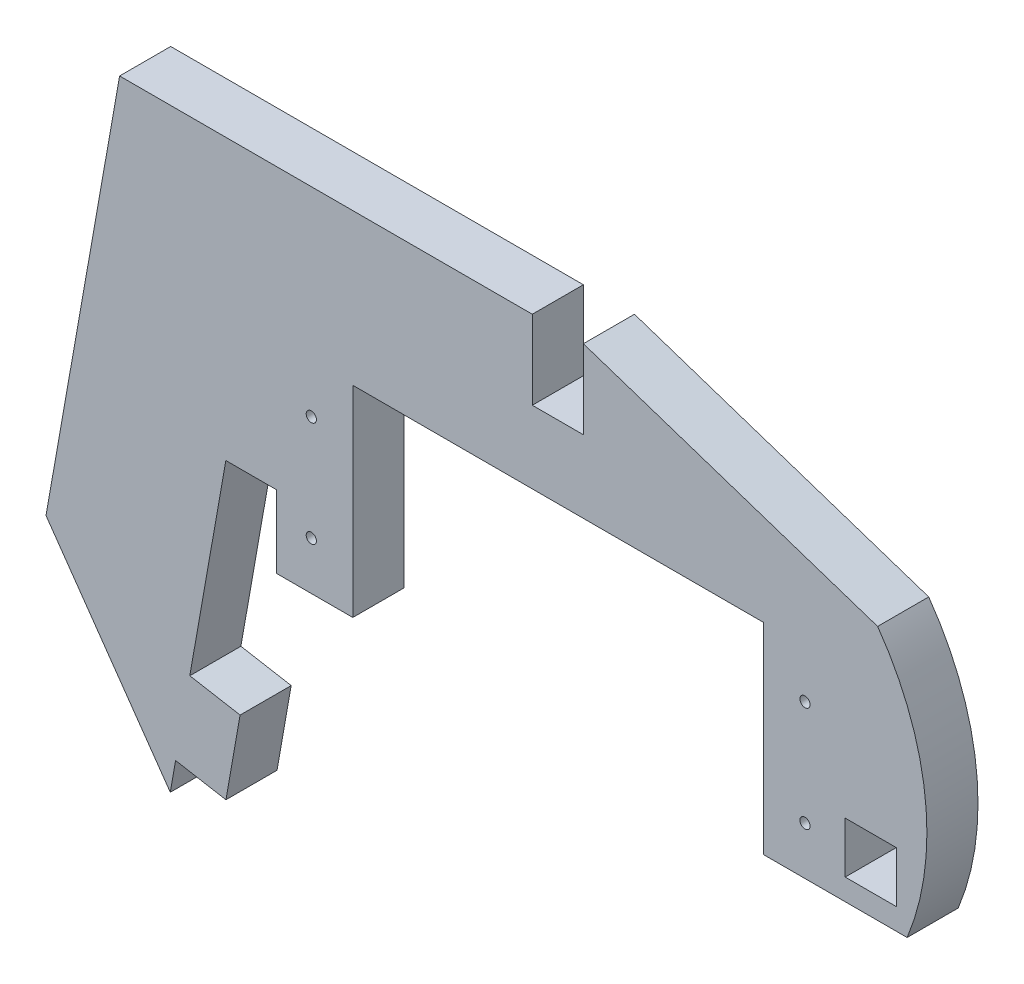
SolidWorks part; units mm, degrees
material "Balsa"
ref_plane "Plan de face" through (0, 0, 0) normal (0, 0, 1) x (1, 0, 0)
ref_plane "Plan de dessus" through (0, 0, 0) normal (0, 1, 0) x (1, 0, 0)
ref_plane "Plan de droite" through (0, 0, 0) normal (1, 0, 0) x (0, 0, -1)
sketch "Esquisse1" plane through (0, 0, 0) normal (0, 0, 1) x (1, 0, 0)
  line L0 (0, 0) -> (0, -19.685)
  line L1 (0, -19.685) -> (20, -19.685)
  line L2 (20, -19.685) -> (20, 2.315)
  line L3 (20, 2.315) -> (-17.6294, 14.8091)
  line L4 (-63.0278, 14.8091) -> (-70.2342, -26.0601)
  line L5 (-17.6294, 14.8091) -> (-63.0278, 14.8091)
  line L6 (-70.2342, -26.0601) -> (-54.011, -49.2292)
  line L7 (-40.2, -19.685) -> (-40.2, 0)
  line L8 (-40.2, 0) -> (0, 0)
  line L10 (-48.8016, -19.685) -> (-40.2, -19.685)
  line L11 (-54.011, -49.2292) -> (-48.8016, -19.685)
  dimension "D1" = 19.685
  dimension "D2" = 40.2
  dimension "D3" = 19.685
  dimension "D4" = 20
  dimension "D5" = 34.4941
  dimension "D6" = 22
  dimension "D7" = 22.5706
  dimension "D8" = 100
  dimension "D9" = 135
  dimension "D10" = 45.3985
  dimension "D11" = 30
  dimension "D12" = 8.6016
extrude "Boss.-Extru.1" add sketch "Esquisse1" along normal blind 5 contours L3 L5 L4 L6 L11 L10 L7 L8 L0 L1 L2
sketch "Esquisse2" plane through (0, 0, 0) normal (0, 0, -1) x (-1, 0, 0)
  line L0 (0, -19.685) -> (-20, -19.685) construction
  line L1 (-20, 2.315) -> (17.6294, 14.8091) construction
  line L2 (-11.1744, 5.2454) -> (-11.9977, 9.9142)
  line L3 (-11.9977, 9.9142) -> (-30.7322, 6.6108)
  line L4 (-30.7322, 6.6108) -> (-25.7328, -21.7423)
  line L5 (-25.7328, -21.7423) -> (-14.065, -19.685)
  line L6 (17.6294, 14.8091) -> (63.0278, 14.8091) construction
  line L7 (-13, -17.5925) -> (-13, -12.5925)
  line L8 (-20, -19.685) -> (-20, 2.315) construction
  line L9 (-13, -17.5925) -> (-8, -17.5925)
  line L10 (-8, -12.5925) -> (-8, -17.5925)
  line L11 (22.6294, 14.8091) -> (17.6294, 14.8091)
  line L12 (-13, -12.5925) -> (-8, -12.5925)
  line L13 (22.6294, 14.8091) -> (22.6294, 7.0925)
  line L14 (22.6294, 7.0925) -> (17.6294, 7.0925)
  line L15 (17.6294, 14.8091) -> (17.6294, 7.0925)
  line L16 (47.693, -34.0964) -> (47.693, -12.5925)
  line L17 (47.693, -12.5925) -> (52.6281, -12.5925)
  line L18 (52.6281, -12.5925) -> (56.1567, -32.6041)
  line L19 (-4.064, -14.986) -> (-4.064, -4.699) construction
  line L20 (56.1567, -32.6041) -> (47.693, -34.0964)
  line L21 (40.2, -19.685) -> (40.2, 0) construction
  line L22 (-4.064, -4.699) -> (44.264, -4.699) construction
  line L23 (44.264, -4.699) -> (44.264, -14.986) construction
  line L24 (0, 0) -> (0, -19.685) construction
  line L25 (48.8016, -19.685) -> (40.2, -19.685) construction
  line L26 (57.5459, -40.4825) -> (58.935, -48.361)
  line L27 (57.5459, -40.4825) -> (52.6218, -41.3508)
  line L28 (58.935, -48.361) -> (54.011, -49.2292)
  line L29 (52.6218, -41.3508) -> (54.011, -49.2292)
  line L30 (70.2342, -26.0601) -> (54.011, -49.2292) construction
  line L31 (54.011, -49.2292) -> (48.8016, -19.685) construction
  line L32 (40.2, -19.685) -> (40.2, 0) construction
  circle A0 centre (-4.064, -14.986) radius 0.5
  arc A1 (-14.065, -19.685) -> (-11.1744, 5.2454) centre (10, -9.8425) cw
  circle A2 centre (-4.064, -4.699) radius 0.5
  circle A3 centre (44.264, -14.986) radius 0.5
  circle A4 centre (44.264, -4.699) radius 0.5
  dimension "D4" = 26
  dimension "D13" = 1
  dimension "D1" = 5
  dimension "D2" = 2.0925
  dimension "D3" = 12
  dimension "D5" = 5
  dimension "D6" = 100
  dimension "D7" = 36.3203
  dimension "D8" = 4.9351
  dimension "D9" = 7.493
  dimension "D10" = 7.0925
  dimension "D11" = 8
  dimension "D12" = 8
  dimension "D14" = 10.287
  dimension "D15" = 4.064
  dimension "D16" = 14.986
  dimension "D17" = 4.064
extrude "Enlèv. mat.-Extru.1" cut sketch "Esquisse2" against normal blind 5
